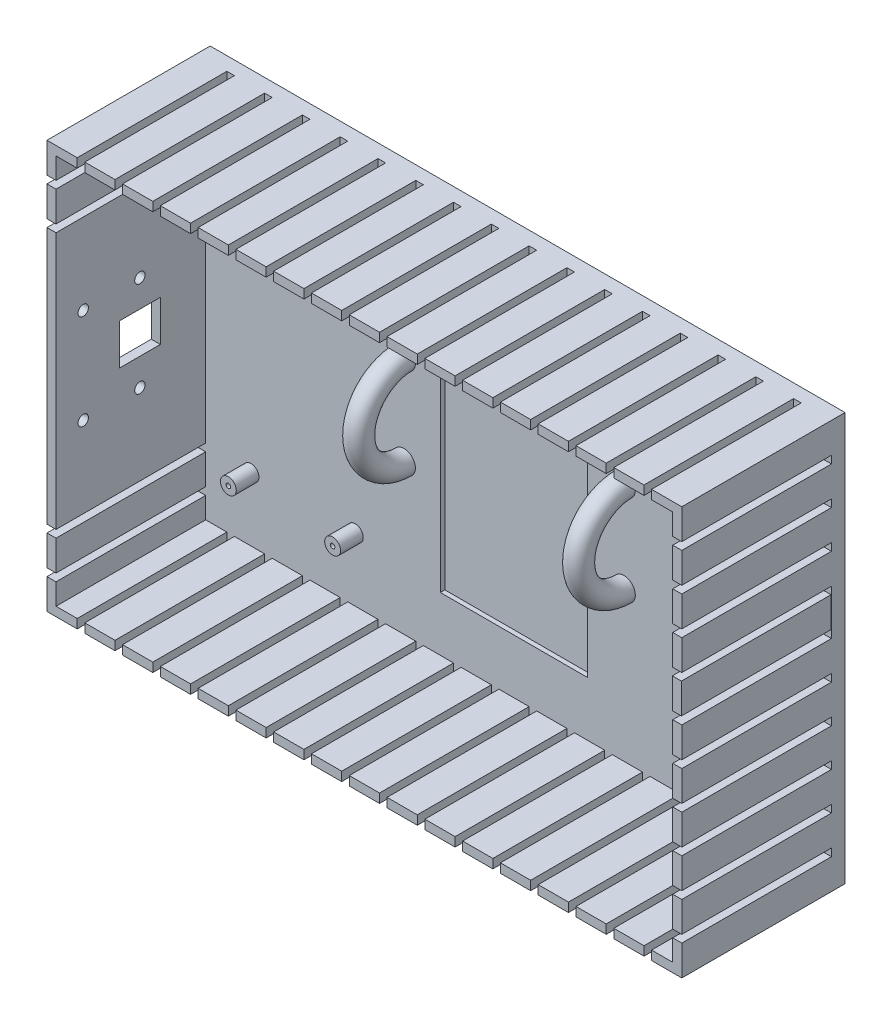
SolidWorks part; units mm, degrees
ref_plane "Front Plane" through (0, 0, 0) normal (1, 0, 0) x (0, 1, 0)
ref_plane "Top Plane" through (0, 0, 0) normal (0, 0, 1) x (0, 1, 0)
ref_plane "Right Plane" through (0, 0, 0) normal (0, 1, 0) x (-1, 0, 0)
sketch "Sketch1" plane through (0, 0, 0) normal (0, 0, 1) x (0, 1, 0)
  line L0 (-45, 0) -> (45, 0) construction
  line L1 (45, -70) -> (-45, -70)
  line L2 (45, -70) -> (45, 70)
  line L3 (45, 70) -> (-45, 70)
  line L4 (-45, -70) -> (-45, 70)
  line L5 (0, 70) -> (0, -70) construction
  point P9 (0, 0)
  dimension "D1" = 140
  dimension "D2" = 90
extrude "Boss-Extrude1" add sketch "Sketch1" along normal blind 3
sketch "Sketch2" plane through (0, 0, 3) normal (0, 0, 1) x (1, 0, 0)
  line L0 (-70, 45) -> (-70, -45) construction
  line L1 (-16.25, 31) -> (16.25, 31)
  line L2 (-16.25, 31) -> (-16.25, -31)
  line L3 (-16.25, -31) -> (16.25, -31)
  line L4 (16.25, 31) -> (16.25, -31)
  line L6 (-70, 0) -> (-16.25, 0) construction
  line L7 (16.25, 0) -> (70, 0) construction
  line L8 (70, -45) -> (70, 45) construction
  line L9 (0, 31) -> (0, 45) construction
  line L10 (70, 45) -> (-70, 45) construction
  line L11 (0, -31) -> (0, -45) construction
  line L12 (-70, -45) -> (70, -45) construction
  dimension "D1" = 62
  dimension "D2" = 32.5
extrude "Cut-Extrude1" cut sketch "Sketch2" against normal blind 1
sketch "Sketch6" plane through (0, 0, 3) normal (0, 0, 1) x (1, 0, 0)
  line L0 (-58, -45) -> (-58, -29) construction
  line L1 (-70, -45) -> (70, -45) construction
  line L2 (-58, 29) -> (-58, 45) construction
  line L3 (70, 45) -> (-70, 45) construction
  line L4 (-70, 45) -> (-70, -45) construction
  circle A0 centre (-58, 29) radius 1.75
  circle A1 centre (-35, 29) radius 1.75
  circle A2 centre (-35, -29) radius 1.75
  circle A3 centre (-58, -29) radius 1.75
  circle A4 centre (-58, 29) radius 0.5
  circle A5 centre (-35, 29) radius 0.5
  circle A6 centre (-58, -29) radius 0.5
  circle A7 centre (-35, -29) radius 0.5
  dimension "D1" = 3.5
  dimension "D2" = 23
  dimension "D3" = 58
  dimension "D4" = 12
  dimension "D5" = 1
extrude "Boss-Extrude2" add sketch "Sketch6" along normal blind 5 contours A1 | A0 | A3 | A2 region at (-59.7005, 29, 3) region at (-36.7005, 29, 3) region at (-36.7005, -29, 3) region at (-59.7005, -29, 3)
extrude "Boss-Extrude3" add sketch "Sketch6<3>" along normal blind 4 contours A4 | A5 | A6 | A7 region at (-58, 29, 3) region at (-35, 29, 3) region at (-58, -29, 3) region at (-35, -29, 3)
sketch "Sketch6<3>" plane through (0, 0, 3) normal (0, 0, 1) x (1, 0, 0) same geometry as "Sketch6"
sketch "Sketch7" plane through (0, 0, 3) normal (0, 0, 1) x (1, 0, 0)
  line L0 (-61.6667, 45) -> (-61.6667, 43)
  line L1 (-70, 45) -> (-63.3333, 45)
  line L2 (-70, 45) -> (-70, 43)
  line L3 (-70, 43) -> (-63.3333, 43)
  line L4 (-63.3333, 45) -> (-63.3333, 43)
  line L5 (-61.6667, 45) -> (-55, 45)
  line L6 (-55, 45) -> (-55, 43)
  line L7 (-61.6667, 43) -> (-55, 43)
  line L8 (-53.3333, 45) -> (-53.3333, 43)
  line L9 (-53.3333, 45) -> (-46.6667, 45)
  line L10 (-46.6667, 45) -> (-46.6667, 43)
  line L11 (-53.3333, 43) -> (-46.6667, 43)
  line L12 (-45, 45) -> (-45, 43)
  line L13 (-45, 45) -> (-38.3333, 45)
  line L14 (-38.3333, 45) -> (-38.3333, 43)
  line L15 (-45, 43) -> (-38.3333, 43)
  line L16 (-36.6667, 45) -> (-36.6667, 43)
  line L17 (-36.6667, 45) -> (-30, 45)
  line L18 (-30, 45) -> (-30, 43)
  line L19 (-36.6667, 43) -> (-30, 43)
  line L20 (-28.3333, 45) -> (-28.3333, 43)
  line L21 (-28.3333, 45) -> (-21.6667, 45)
  line L22 (-21.6667, 45) -> (-21.6667, 43)
  line L23 (-28.3333, 43) -> (-21.6667, 43)
  line L24 (-20, 45) -> (-20, 43)
  line L25 (-20, 45) -> (-13.3333, 45)
  line L26 (-13.3333, 45) -> (-13.3333, 43)
  line L27 (-20, 43) -> (-13.3333, 43)
  line L28 (-11.6667, 45) -> (-11.6667, 43)
  line L29 (-11.6667, 45) -> (-5, 45)
  line L30 (-5, 45) -> (-5, 43)
  line L31 (-11.6667, 43) -> (-5, 43)
  line L32 (-3.3333, 45) -> (-3.3333, 43)
  line L33 (-3.3333, 45) -> (3.3333, 45)
  line L34 (3.3333, 45) -> (3.3333, 43)
  line L35 (-3.3333, 43) -> (3.3333, 43)
  line L36 (5, 45) -> (5, 43)
  line L37 (5, 45) -> (11.6667, 45)
  line L38 (11.6667, 45) -> (11.6667, 43)
  line L39 (5, 43) -> (11.6667, 43)
  line L40 (13.3333, 45) -> (13.3333, 43)
  line L41 (13.3333, 45) -> (20, 45)
  line L42 (20, 45) -> (20, 43)
  line L43 (13.3333, 43) -> (20, 43)
  line L44 (21.6667, 45) -> (21.6667, 43)
  line L45 (21.6667, 45) -> (28.3333, 45)
  line L46 (28.3333, 45) -> (28.3333, 43)
  line L47 (21.6667, 43) -> (28.3333, 43)
  line L48 (30, 45) -> (30, 43)
  line L49 (30, 45) -> (36.6667, 45)
  line L50 (36.6667, 45) -> (36.6667, 43)
  line L51 (30, 43) -> (36.6667, 43)
  line L52 (38.3333, 45) -> (38.3333, 43)
  line L53 (38.3333, 45) -> (45, 45)
  line L54 (45, 45) -> (45, 43)
  line L55 (38.3333, 43) -> (45, 43)
  line L56 (46.6667, 45) -> (46.6667, 43)
  line L57 (46.6667, 45) -> (53.3333, 45)
  line L58 (53.3333, 45) -> (53.3333, 43)
  line L59 (46.6667, 43) -> (53.3333, 43)
  line L60 (55, 45) -> (55, 43)
  line L61 (55, 45) -> (61.6667, 45)
  line L62 (61.6667, 45) -> (61.6667, 43)
  line L63 (55, 43) -> (61.6667, 43)
  line L64 (63.3333, 45) -> (63.3333, 43)
  line L65 (63.3333, 45) -> (70, 45)
  line L66 (70, 45) -> (70, 43)
  line L67 (63.3333, 43) -> (70, 43)
  line L68 (-70, 36.6667) -> (-70, 30)
  line L69 (-70, 45) -> (-68, 45)
  line L70 (-70, 45) -> (-70, 38.3333)
  line L71 (-70, 38.3333) -> (-68, 38.3333)
  line L72 (-68, 45) -> (-68, 38.3333)
  line L73 (-70, 36.6667) -> (-68, 36.6667)
  line L74 (-68, 36.6667) -> (-68, 30)
  line L75 (-70, 30) -> (-68, 30)
  line L104 (-70, -30) -> (-70, -36.6667)
  line L105 (-70, -30) -> (-68, -30)
  line L106 (-68, -30) -> (-68, -36.6667)
  line L107 (-70, -36.6667) -> (-68, -36.6667)
  line L108 (-70, -38.3333) -> (-70, -45)
  line L109 (-70, -38.3333) -> (-68, -38.3333)
  line L110 (-68, -38.3333) -> (-68, -45)
  line L111 (-70, -45) -> (-68, -45)
  line L112 (0, 0) -> (0, 18.2112) construction
  line L113 (0, 0) -> (-20.7335, 0) construction
  line L114 (13.3333, -45) -> (20, -45)
  line L115 (20, -45) -> (20, -43)
  line L116 (13.3333, -43) -> (20, -43)
  line L117 (13.3333, -45) -> (13.3333, -43)
  line L118 (21.6667, -45) -> (28.3333, -45)
  line L119 (28.3333, -45) -> (28.3333, -43)
  line L120 (21.6667, -43) -> (28.3333, -43)
  line L121 (21.6667, -45) -> (21.6667, -43)
  line L122 (30, -45) -> (36.6667, -45)
  line L123 (36.6667, -45) -> (36.6667, -43)
  line L124 (30, -43) -> (36.6667, -43)
  line L125 (30, -45) -> (30, -43)
  line L126 (38.3333, -45) -> (45, -45)
  line L127 (45, -45) -> (45, -43)
  line L128 (38.3333, -43) -> (45, -43)
  line L129 (38.3333, -45) -> (38.3333, -43)
  line L130 (46.6667, -45) -> (53.3333, -45)
  line L131 (53.3333, -45) -> (53.3333, -43)
  line L132 (46.6667, -43) -> (53.3333, -43)
  line L133 (46.6667, -45) -> (46.6667, -43)
  line L134 (55, -45) -> (61.6667, -45)
  line L135 (61.6667, -45) -> (61.6667, -43)
  line L136 (55, -43) -> (61.6667, -43)
  line L137 (55, -45) -> (55, -43)
  line L138 (63.3333, -45) -> (70, -45)
  line L139 (70, -45) -> (70, -43)
  line L140 (63.3333, -43) -> (70, -43)
  line L141 (63.3333, -45) -> (63.3333, -43)
  line L142 (5, -45) -> (11.6667, -45)
  line L143 (11.6667, -45) -> (11.6667, -43)
  line L144 (5, -43) -> (11.6667, -43)
  line L145 (5, -45) -> (5, -43)
  line L146 (-3.3333, -45) -> (3.3333, -45)
  line L147 (3.3333, -45) -> (3.3333, -43)
  line L148 (-3.3333, -43) -> (3.3333, -43)
  line L149 (-3.3333, -45) -> (-3.3333, -43)
  line L150 (-11.6667, -45) -> (-5, -45)
  line L151 (-5, -45) -> (-5, -43)
  line L152 (-11.6667, -43) -> (-5, -43)
  line L153 (-11.6667, -45) -> (-11.6667, -43)
  line L154 (-20, -45) -> (-13.3333, -45)
  line L155 (-13.3333, -45) -> (-13.3333, -43)
  line L156 (-20, -43) -> (-13.3333, -43)
  line L157 (-20, -45) -> (-20, -43)
  line L158 (-28.3333, -45) -> (-21.6667, -45)
  line L159 (-21.6667, -45) -> (-21.6667, -43)
  line L160 (-28.3333, -43) -> (-21.6667, -43)
  line L161 (-28.3333, -45) -> (-28.3333, -43)
  line L162 (-36.6667, -45) -> (-30, -45)
  line L163 (-30, -45) -> (-30, -43)
  line L164 (-36.6667, -43) -> (-30, -43)
  line L165 (-36.6667, -45) -> (-36.6667, -43)
  line L166 (-70, -43) -> (-63.3333, -43)
  line L167 (-63.3333, -45) -> (-63.3333, -43)
  line L168 (-70, -45) -> (-63.3333, -45)
  line L169 (-70, -45) -> (-70, -43)
  line L170 (-61.6667, -45) -> (-55, -45)
  line L171 (-55, -45) -> (-55, -43)
  line L172 (-61.6667, -43) -> (-55, -43)
  line L173 (-61.6667, -45) -> (-61.6667, -43)
  line L174 (-53.3333, -45) -> (-46.6667, -45)
  line L175 (-46.6667, -45) -> (-46.6667, -43)
  line L176 (-53.3333, -43) -> (-46.6667, -43)
  line L177 (-53.3333, -45) -> (-53.3333, -43)
  line L178 (-45, -45) -> (-38.3333, -45)
  line L179 (-38.3333, -45) -> (-38.3333, -43)
  line L180 (-45, -43) -> (-38.3333, -43)
  line L181 (-45, -45) -> (-45, -43)
  line L182 (70, 28.3333) -> (68, 28.3333)
  line L183 (68, 28.3333) -> (68, 21.6667)
  line L184 (70, 21.6667) -> (68, 21.6667)
  line L185 (70, 28.3333) -> (70, 21.6667)
  line L186 (70, 36.6667) -> (68, 36.6667)
  line L187 (68, 36.6667) -> (68, 30)
  line L188 (70, 30) -> (68, 30)
  line L189 (70, 36.6667) -> (70, 30)
  line L190 (70, 38.3333) -> (68, 38.3333)
  line L191 (68, 45) -> (68, 38.3333)
  line L192 (70, 45) -> (68, 45)
  line L193 (70, 45) -> (70, 38.3333)
  line L194 (70, 20) -> (68, 20)
  line L195 (68, 20) -> (68, 13.3333)
  line L196 (70, 13.3333) -> (68, 13.3333)
  line L197 (70, 20) -> (70, 13.3333)
  line L198 (69.9175, 11.6667) -> (67.9175, 11.6667)
  line L199 (67.9175, 11.6667) -> (67.9175, 5)
  line L200 (69.9175, 5) -> (67.9175, 5)
  line L201 (69.9175, 11.6667) -> (69.9175, 5)
  line L202 (70, 3.3333) -> (68, 3.3333)
  line L203 (68, 3.3333) -> (68, -3.3333)
  line L204 (70, -3.3333) -> (68, -3.3333)
  line L205 (70, 3.3333) -> (70, -3.3333)
  line L206 (70, -5) -> (68, -5)
  line L207 (68, -5) -> (68, -11.6667)
  line L208 (70, -11.6667) -> (68, -11.6667)
  line L209 (70, -5) -> (70, -11.6667)
  line L210 (70, -13.3333) -> (68, -13.3333)
  line L211 (68, -13.3333) -> (68, -20)
  line L212 (70, -20) -> (68, -20)
  line L213 (70, -13.3333) -> (70, -20)
  line L214 (70, -21.6667) -> (68, -21.6667)
  line L215 (68, -21.6667) -> (68, -28.3333)
  line L216 (70, -28.3333) -> (68, -28.3333)
  line L217 (70, -21.6667) -> (70, -28.3333)
  line L218 (70, -30) -> (68, -30)
  line L219 (68, -30) -> (68, -36.6667)
  line L220 (70, -36.6667) -> (68, -36.6667)
  line L221 (70, -30) -> (70, -36.6667)
  line L222 (70, -38.3333) -> (68, -38.3333)
  line L223 (68, -38.3333) -> (68, -45)
  line L224 (70, -45) -> (68, -45)
  line L225 (70, -38.3333) -> (70, -45)
  line L226 (-70, 28.3333) -> (-60.5263, 28.3333) construction
  line L227 (-70, -28.3333) -> (-61.2912, -28.3333) construction
  line L229 (-70, 28.3333) -> (-68, 28.3333)
  line L230 (-70, 28.3333) -> (-70, -28.3333)
  line L231 (-70, -28.3333) -> (-68, -28.3333)
  line L232 (-68, 28.3333) -> (-68, -28.3333)
  line M13 (70, 45) -> (-70, 45)
  line M14 (-70, 45) -> (-70, -45)
  line M15 (-70, -45) -> (70, -45)
  line M16 (70, -45) -> (70, 45)
  dimension "D1" = 6.6667
  dimension "D2" = 2
  dimension "D5" = 1.6667
  dimension "D4" = 1.6667
  dimension "D3" = 17
extrude "Boss-Extrude6" add sketch "Sketch7" along normal blind 33 contours L75 L74 L73 M14 | L72 L3 L71 M14 | L201 L198 L199 L200 | L166 L110 L109 M14 | L167 L166 L110 M15 | L173 L171 L172 M15 | L177 L175 L176 M15 | L165 L163 L164 M15 | L161 L159 L160 M15 | L149 L147 L148 M15 | L145 L143 L144 M15 | L117 L115 L116 M15 | L121 L119 L120 M15 | L129 L127 L128 M15 | L133 L131 L132 M15 | L222 L223 L140 M16 | L204 L202 L203 M16 | L208 L206 L207 M16 | L212 L210 L211 M16 | L216 L214 L215 M16 | L220 L218 L219 M16 | L184 L182 L183 M16 | L188 L186 L187 M16 | L67 L191 L190 M16 | L191 L67 M13 M16 | L191 L65 L64 L67 | L60 L63 L62 M13 | L56 L59 L58 M13 | L52 L55 L54 M13 | L48 L51 L50 M13 | L44 L47 L46 M13 | L72 L3 L4 M13 | L0 L7 L6 M13 | L8 L11 L10 M13 | L12 L15 L14 M13 | L16 L19 L18 M13 | L20 L23 L22 M13 | L24 L27 L26 M13 | L28 L31 L30 M13 | L32 L35 L34 M13 | L36 L39 L38 M13 | L40 L43 L42 M13 | L72 L1 L3 M14 | L166 L108 L110 M15 | L232 L229 L231 M14 | L104 L107 L106 L105 | L197 L196 L195 L194 | L178 L179 L180 L181 | L156 L155 L154 L157 | L150 L151 L152 L153 | L122 L123 L124 L125 | L134 L135 L136 L137 | L139 L140 L141 L138 region at (-58.3333, 44, 3) region at (-65.6667, 44, 3) region at (-50, 44, 3) region at (-69, 44, 3) region at (-69, 40.6667, 3) region at (-41.6667, 44, 3) region at (-33.3333, 44, 3) region at (-69, 33.3333, 3) region at (-25, 44, 3) region at (-69, 0, 3) region at (-16.6667, 44, 3) region at (-8.3333, 44, 3) region at (-69, -40.6667, 3) region at (-69, -44, 3) region at (0, 44, 3) region at (-65.6667, -44, 3) region at (8.3333, 44, 3) region at (-58.3333, -44, 3) region at (16.6667, 44, 3) region at (-50, -44, 3) region at (25, 44, 3) region at (33.3333, 44, 3) region at (-33.3333, -44, 3) region at (41.6667, 44, 3) region at (-25, -44, 3) region at (50, 44, 3) region at (58.3333, 44, 3) region at (65.6667, 44, 3) region at (69, 44, 3) region at (0, -44, 3) region at (69, 40.6667, 3) region at (8.3333, -44, 3) region at (69, 33.3333, 3) region at (16.6667, -44, 3) region at (69, 25, 3) region at (25, -44, 3) region at (69, 0, 3) region at (41.6667, -44, 3) region at (69, -8.3333, 3) region at (50, -44, 3) region at (69, -16.6667, 3) region at (69, -25, 3) region at (69, -33.3333, 3) region at (69, -40.6667, 3) region at (68.9175, 8.3333, 3)
sketch "Sketch9" plane through (0, 0, 3) normal (0, 0, 1) x (1, 0, 0)
  line L0 (-36.3093, 0) -> (22.5747, 0) construction
  line L1 (0, 0) -> (0, 22.2066) construction
  line L2 (-16.25, 31) -> (-16.25, -31) construction
  circle A0 centre (-24.25, -10) radius 2.5
  circle A1 centre (24.25, -10) radius 2.5
  dimension "D1" = 5
  dimension "D2" = 10
  dimension "D3" = 8
revolve "Revolve3" add sketch "Sketch9" angle 180 about L0 reverse direction yes
sketch "Sketch11" plane through (-68, 0, 0) normal (1, 0, 0) x (0, 1, 0)
  line L0 (28.3333, 36) -> (-28.3333, 36) construction
  line L1 (-4.5, 22) -> (4.5, 22)
  line L2 (-4.5, 22) -> (-4.5, 13)
  line L3 (-4.5, 13) -> (4.5, 13)
  line L4 (4.5, 22) -> (4.5, 13)
  line L5 (-4.5, 17.5) -> (-28.3333, 17.5) construction
  line L6 (-28.3333, 36) -> (-28.3333, 3) construction
  line L7 (4.5, 17.5) -> (28.3333, 17.5) construction
  line L8 (28.3333, 36) -> (28.3333, 3) construction
  line L9 (0, 36) -> (0, 3) construction
  line L10 (28.3333, 3) -> (-28.3333, 3) construction
  circle A0 centre (-10.5, 30) radius 1.15
  circle A1 centre (10.5, 30) radius 1.15
  circle A2 centre (10.5, 17.5) radius 1.15
  circle A3 centre (-10.5, 17.5) radius 1.15
  point P16 (0, 0)
  point P25 (0, 36)
  dimension "D2" = 12.5
  dimension "D4" = 2.3
  dimension "D1" = 21
  dimension "D5" = 9
  dimension "D6" = 14
extrude "Cut-Extrude2" cut sketch "Sketch11" against normal through all contours A0 | A3 | A1 | A2 | L2 L3 L4 L1 region at (-68, -10.5, 30) region at (-68, 10.5, 30) region at (-68, 10.5, 17.5) region at (-68, -10.5, 17.5)
